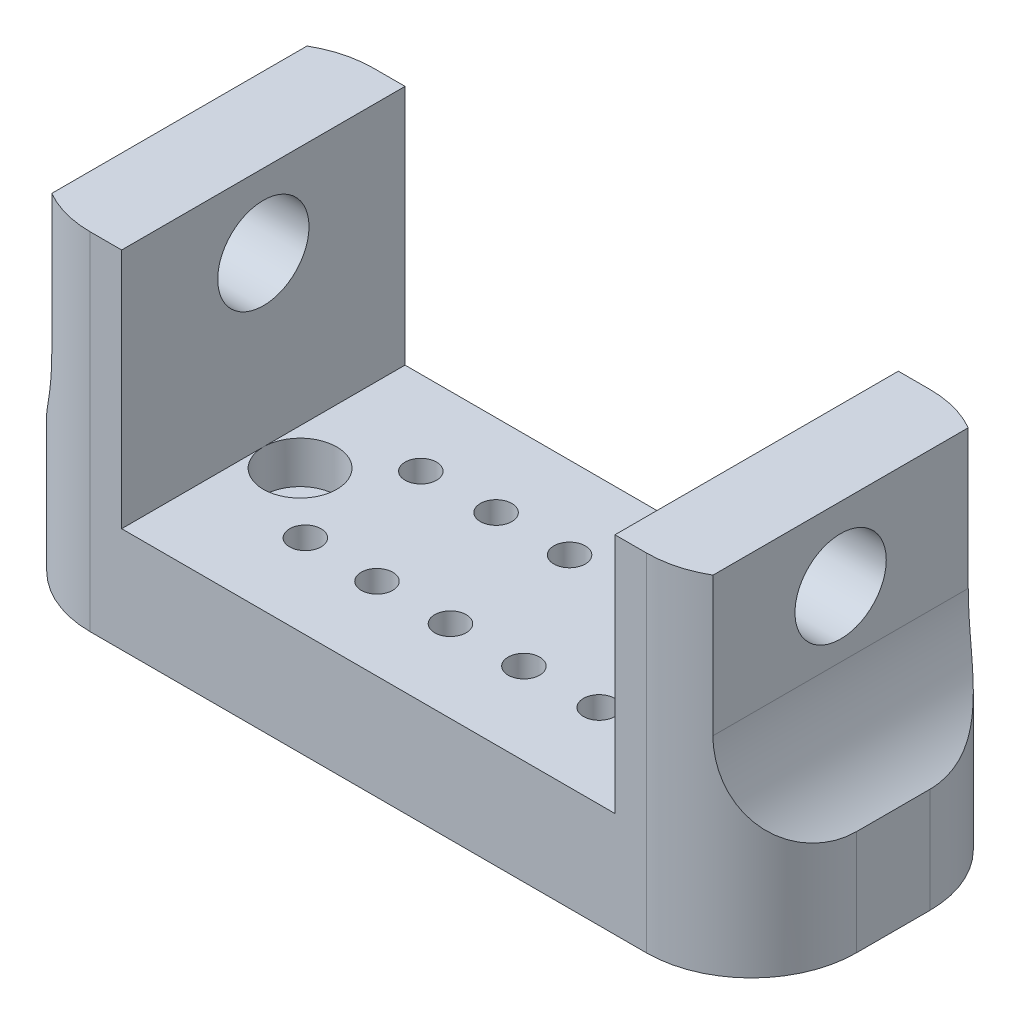
SolidWorks part; units mm, degrees
ref_plane "Front Plane" through (0, 0, 0) normal (0, 0, 1) x (1, 0, 0)
ref_plane "Top Plane" through (0, 0, 0) normal (0, 1, 0) x (1, 0, 0)
ref_plane "Right Plane" through (0, 0, 0) normal (1, 0, 0) x (0, 0, -1)
sketch "Sketch1" plane through (0, 0, 0) normal (0, 1, 0) x (1, 0, 0)
  line L0 (36.5, 27) -> (36.5, 0) construction
  line L1 (0, 0) -> (73, 0)
  line L2 (0, 0) -> (0, 27)
  line L3 (0, 27) -> (73, 27)
  line L4 (73, 0) -> (73, 27)
  line L5 (0, 13.5) -> (73, 13.5) construction
  dimension "D1" = 73
  dimension "D2" = 27
extrude "Boss-Extrude1" add sketch "Sketch1" along normal blind 10
sketch "Sketch2" plane through (0, 0, 0) normal (0, -1, 0) x (1, 0, 0)
  line L0 (0, -13.5) -> (73, -13.5) construction
  line L1 (0, -27) -> (0, 0) construction
  line L2 (73, 0) -> (73, -27) construction
  line L3 (36.5, 0) -> (36.5, -27) construction
  line L4 (0, 0) -> (73, 0) construction
  line L5 (73, -27) -> (0, -27) construction
  line L6 (60, -27) -> (68, -27)
  line L7 (13, 0) -> (5, 0)
  line L8 (13, 0) -> (13, -27)
  line L9 (13, -27) -> (5, -27)
  line L10 (5, 0) -> (5, -27)
  line L11 (68, 0) -> (68, -27)
  line L12 (60, 0) -> (68, 0)
  line L13 (60, 0) -> (60, -27)
  dimension "D1" = 47
  dimension "D2" = 8
extrude "Boss-Extrude2" add sketch "Sketch2" against normal blind 33
sketch "Sketch3" plane through (68, 0, 0) normal (1, 0, 0) x (0, 0, -1)
  line L0 (13.5, 33) -> (13.5, 10) construction
  line L1 (27, 33) -> (0, 33) construction
  line L2 (27, 10) -> (0, 10) construction
  line L3 (0, 33) -> (0, 10) construction
  circle A0 centre (13.5, 26) radius 4.35
  dimension "D1" = 8.7
  dimension "D2" = 7
  dimension "D3" = 13.5
extrude "Cut-Extrude1" cut sketch "Sketch3" against normal through all
fillet "Fillet1" radius 10 4 edges at (73, 5, 0) (0, 5, 0) (0, 5, -27) (73, 5, -27)
sketch "Sketch4" plane through (0, 0, 0) normal (0, -1, 0) x (1, 0, 0)
  line L0 (0, -13.5) -> (73, -13.5) construction
  line L1 (0, -17) -> (0, -10) construction
  line L2 (73, -10) -> (73, -17) construction
  line L3 (36.5, 0) -> (36.5, -27) construction
  line L4 (10, 0) -> (63, 0) construction
  line L5 (63, -27) -> (10, -27) construction
  circle A0 centre (16.5, -13.5) radius 1.75
  circle A1 centre (56.5, -13.5) radius 1.75
  dimension "D1" = 3.5
  dimension "D2" = 40
extrude "Cut-Extrude2" cut sketch "Sketch4" against normal blind 30
sketch "Sketch5" plane through (0, 10, 0) normal (0, 1, 0) x (1, 0, 0)
  line L0 (36.5, 27) -> (36.5, 0) construction
  line L1 (60, 27) -> (13, 27) construction
  line L2 (13, 0) -> (60, 0) construction
  circle A0 centre (16.5, 13.5) radius 3.5
  circle A1 centre (56.5, 13.5) radius 3.5
  dimension "D1" = 7
extrude "Cut-Extrude3" cut sketch "Sketch5" against normal blind 4
sketch "Sketch6" plane through (0, 10, 0) normal (0, 1, 0) x (1, 0, 0)
  line L0 (0, 13.5) -> (73, 13.5) construction
  line L1 (0, 17) -> (0, 10) construction
  line L2 (73, 10) -> (73, 17) construction
  line L3 (36.5, 27) -> (36.5, 0) construction
  line L4 (60, 27) -> (13, 27) construction
  line L5 (13, 0) -> (60, 0) construction
  line L6 (13, 27) -> (13, 0) construction
  circle A0 centre (36.5, 19.1745) radius 1.5
  circle A1 centre (29.5, 19.1745) radius 1.5
  circle A2 centre (22.5022, 19) radius 1.5
  circle A3 centre (43.5, 19.1745) radius 1.5
  circle A4 centre (50.4978, 19) radius 1.5
  circle A5 centre (50.4978, 8) radius 1.5
  circle A6 centre (43.5, 7.8255) radius 1.5
  circle A7 centre (36.5, 7.8255) radius 1.5
  circle A8 centre (29.5, 7.8255) radius 1.5
  circle A9 centre (22.5022, 8) radius 1.5
  dimension "D1" = 3
  dimension "D2" = 7
  dimension "D3" = 7
  dimension "D4" = 11
  dimension "D5" = 9.5022
  dimension "D6" = 16.5
extrude "Cut-Extrude4" cut sketch "Sketch6" against normal through all
fillet "Fillet2" radius 12 2 edges at (5, 10, -13.5) (68, 10, -13.5)
